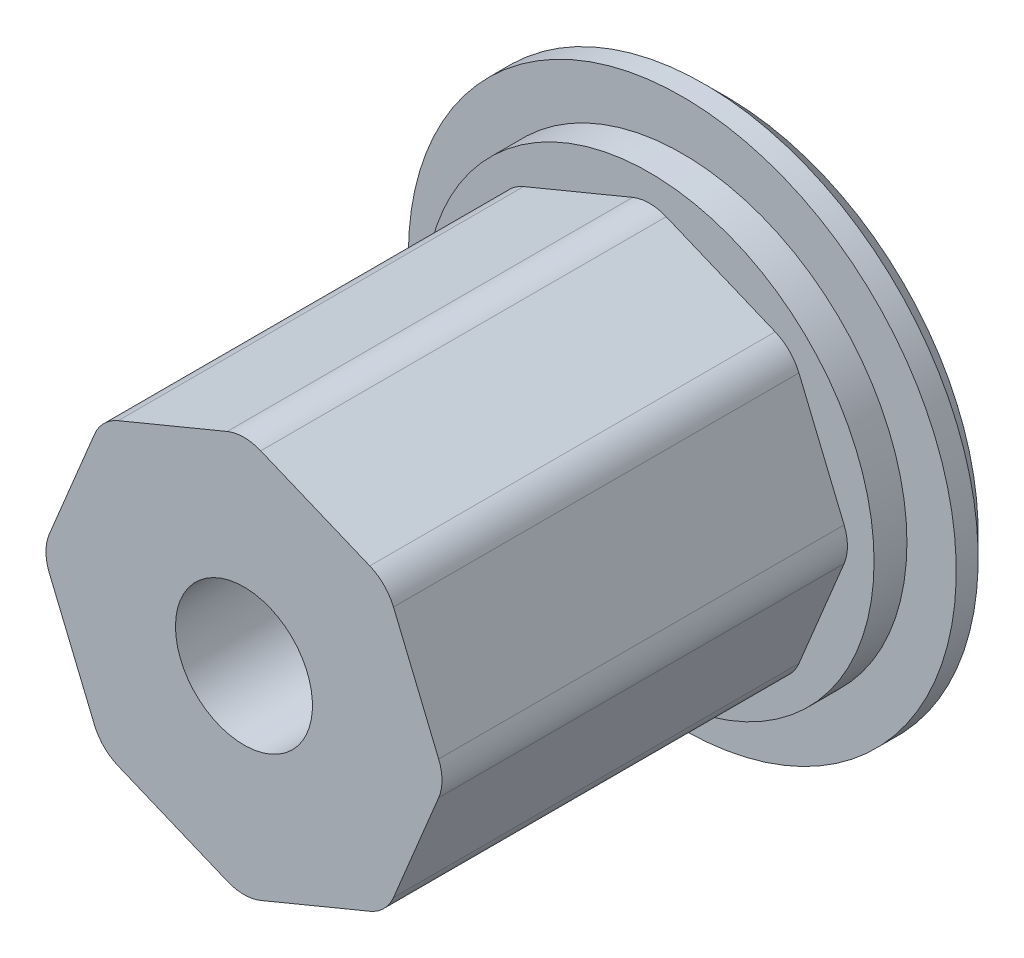
SolidWorks part; units mm, degrees
material "1.2210 (115CrV3)"
ref_plane "Front Plane" through (0, 0, 0) normal (0, 0, 1) x (1, 0, 0)
ref_plane "Top Plane" through (0, 0, 0) normal (0, 1, 0) x (1, 0, 0)
ref_plane "Right Plane" through (0, 0, 0) normal (1, 0, 0) x (0, 0, -1)
sketch "Sketch1" plane through (0, 0, 0) normal (0, 0, 1) x (1, 0, 0)
  line L0 (-12.5, 10.5) -> (-12.5, -10.5)
  line L1 (-10.5, 12.5) -> (10.5, 12.5)
  line L2 (-10.5, -12.5) -> (10.5, -12.5)
  line L3 (12.5, 10.5) -> (12.5, -10.5)
  line L4 (-12.5, 12.5) -> (12.5, -12.5) construction
  line L5 (-12.5, -12.5) -> (12.5, 12.5) construction
  line L6 (0, -14.0711) -> (0, 14.0711) construction
  line L7 (-13.6453, 11.4805) -> (-17.7666, 1.5307)
  line L8 (-17.7666, -1.5307) -> (-13.6453, -11.4805)
  line L9 (-11.4805, -13.6453) -> (-1.5307, -17.7666)
  line L10 (1.5307, -17.7666) -> (11.4805, -13.6453)
  line L11 (13.6453, -11.4805) -> (17.7666, -1.5307)
  line L12 (17.7666, 1.5307) -> (13.6453, 11.4805)
  line L13 (11.4805, 13.6453) -> (1.5307, 17.7666)
  line L14 (-1.5307, 17.7666) -> (-11.4805, 13.6453)
  circle A0 centre (0, 0) radius 17 construction
  arc A1 (10.5, -12.5) -> (12.5, -10.5) centre (10.5, -10.5) ccw
  arc A2 (-12.5, -10.5) -> (-10.5, -12.5) centre (-10.5, -10.5) ccw
  arc A3 (10.5, 12.5) -> (12.5, 10.5) centre (10.5, 10.5) cw
  arc A4 (-10.5, 12.5) -> (-12.5, 10.5) centre (-10.5, 10.5) ccw
  arc A5 (-13.6453, 11.4805) -> (-11.4805, 13.6453) centre (-9.9498, 9.9498) cw
  arc A6 (-17.7666, 1.5307) -> (-17.7666, -1.5307) centre (-14.0711, 0) ccw
  arc A7 (-13.6453, -11.4805) -> (-11.4805, -13.6453) centre (-9.9498, -9.9498) ccw
  arc A8 (-1.5307, -17.7666) -> (1.5307, -17.7666) centre (0, -14.0711) ccw
  arc A9 (11.4805, -13.6453) -> (13.6453, -11.4805) centre (9.9498, -9.9498) ccw
  arc A10 (17.7666, -1.5307) -> (17.7666, 1.5307) centre (14.0711, 0) ccw
  arc A11 (13.6453, 11.4805) -> (11.4805, 13.6453) centre (9.9498, 9.9498) ccw
  arc A12 (1.5307, 17.7666) -> (-1.5307, 17.7666) centre (0, 14.0711) ccw
  point P43 (0, 0)
  dimension "D1" = 2
  dimension "D3" = 4
  dimension "D4" = 34
  dimension "D2" = 25
extrude "Boss-Extrude1" add sketch "Sketch1" along normal blind 23
sketch "Sketch3" plane through (0, 0, 23) normal (0, 0, 1) x (1, 0, 0)
  line L8 (-1.5307, 17.7666) -> (-11.4805, 13.6453)
  line L9 (11.4805, 13.6453) -> (1.5307, 17.7666)
  line L10 (17.7666, 1.5307) -> (13.6453, 11.4805)
  line L11 (13.6453, -11.4805) -> (17.7666, -1.5307)
  line L12 (1.5307, -17.7666) -> (11.4805, -13.6453)
  line L13 (-11.4805, -13.6453) -> (-1.5307, -17.7666)
  line L14 (-17.7666, -1.5307) -> (-13.6453, -11.4805)
  line L15 (-13.6453, 11.4805) -> (-17.7666, 1.5307)
  line L16 (-1.5307, 17.7666) -> (-11.4805, 13.6453)
  line L17 (11.4805, 13.6453) -> (1.5307, 17.7666)
  line L18 (17.7666, 1.5307) -> (13.6453, 11.4805)
  line L19 (13.6453, -11.4805) -> (17.7666, -1.5307)
  line L20 (1.5307, -17.7666) -> (11.4805, -13.6453)
  line L21 (-11.4805, -13.6453) -> (-1.5307, -17.7666)
  line L22 (-17.7666, -1.5307) -> (-13.6453, -11.4805)
  line L23 (-13.6453, 11.4805) -> (-17.7666, 1.5307)
  circle A0 centre (0, 0) radius 6.25
  arc A8 (-11.4805, 13.6453) -> (-13.6453, 11.4805) centre (-9.9498, 9.9498) ccw
  arc A9 (1.5307, 17.7666) -> (-1.5307, 17.7666) centre (0, 14.0711) ccw
  arc A10 (13.6453, 11.4805) -> (11.4805, 13.6453) centre (9.9498, 9.9498) ccw
  arc A11 (17.7666, -1.5307) -> (17.7666, 1.5307) centre (14.0711, 0) ccw
  arc A12 (11.4805, -13.6453) -> (13.6453, -11.4805) centre (9.9498, -9.9498) ccw
  arc A13 (-1.5307, -17.7666) -> (1.5307, -17.7666) centre (0, -14.0711) ccw
  arc A14 (-13.6453, -11.4805) -> (-11.4805, -13.6453) centre (-9.9498, -9.9498) ccw
  arc A15 (-17.7666, 1.5307) -> (-17.7666, -1.5307) centre (-14.0711, 0) ccw
  arc A16 (-11.4805, 13.6453) -> (-13.6453, 11.4805) centre (-9.9498, 9.9498) ccw
  arc A17 (1.5307, 17.7666) -> (-1.5307, 17.7666) centre (0, 14.0711) ccw
  arc A18 (13.6453, 11.4805) -> (11.4805, 13.6453) centre (9.9498, 9.9498) ccw
  arc A19 (17.7666, -1.5307) -> (17.7666, 1.5307) centre (14.0711, 0) ccw
  arc A20 (11.4805, -13.6453) -> (13.6453, -11.4805) centre (9.9498, -9.9498) ccw
  arc A21 (-1.5307, -17.7666) -> (1.5307, -17.7666) centre (0, -14.0711) ccw
  arc A22 (-13.6453, -11.4805) -> (-11.4805, -13.6453) centre (-9.9498, -9.9498) ccw
  arc A23 (-17.7666, 1.5307) -> (-17.7666, -1.5307) centre (-14.0711, 0) ccw
  dimension "D2" = 12.5
  dimension "D1" = 0
extrude "Boss-Extrude2" add sketch "Sketch3" along normal offset from surface (17 mm away) 40 up to face at (0, 0, 0)
sketch "Sketch7" plane through (0, 0, 0) normal (0, 0, -1) x (-1, 0, 0)
  line L1 (-11.4805, 13.6453) -> (-1.5307, 17.7666) construction
  line L2 (-17.7666, 1.5307) -> (-13.6453, 11.4805) construction
  line L3 (-13.6453, -11.4805) -> (-17.7666, -1.5307) construction
  line L4 (-1.5307, -17.7666) -> (-11.4805, -13.6453) construction
  line L5 (11.4805, -13.6453) -> (1.5307, -17.7666) construction
  line L6 (17.7666, -1.5307) -> (13.6453, -11.4805) construction
  line L7 (13.6453, 11.4805) -> (17.7666, 1.5307) construction
  line L8 (1.5307, 17.7666) -> (11.4805, 13.6453) construction
  line L9 (-11.4805, 13.6453) -> (-1.5307, 17.7666)
  line L10 (-17.7666, 1.5307) -> (-13.6453, 11.4805)
  line L11 (-13.6453, -11.4805) -> (-17.7666, -1.5307)
  line L12 (-1.5307, -17.7666) -> (-11.4805, -13.6453)
  line L13 (11.4805, -13.6453) -> (1.5307, -17.7666)
  line L14 (17.7666, -1.5307) -> (13.6453, -11.4805)
  line L15 (13.6453, 11.4805) -> (17.7666, 1.5307)
  line L16 (1.5307, 17.7666) -> (11.4805, 13.6453)
  circle A0 centre (0, 0) radius 20.5
  arc A1 (-11.4805, 13.6453) -> (-13.6453, 11.4805) centre (-9.9498, 9.9498) ccw construction
  arc A2 (-17.7666, 1.5307) -> (-17.7666, -1.5307) centre (-14.0711, 0) ccw construction
  arc A3 (-13.6453, -11.4805) -> (-11.4805, -13.6453) centre (-9.9498, -9.9498) ccw construction
  arc A4 (-1.5307, -17.7666) -> (1.5307, -17.7666) centre (0, -14.0711) ccw construction
  arc A5 (11.4805, -13.6453) -> (13.6453, -11.4805) centre (9.9498, -9.9498) ccw construction
  arc A6 (17.7666, -1.5307) -> (17.7666, 1.5307) centre (14.0711, 0) ccw construction
  arc A7 (13.6453, 11.4805) -> (11.4805, 13.6453) centre (9.9498, 9.9498) ccw construction
  arc A8 (1.5307, 17.7666) -> (-1.5307, 17.7666) centre (0, 14.0711) ccw construction
  arc A9 (-11.4805, 13.6453) -> (-13.6453, 11.4805) centre (-9.9498, 9.9498) ccw
  arc A10 (-17.7666, 1.5307) -> (-17.7666, -1.5307) centre (-14.0711, 0) ccw
  arc A11 (-13.6453, -11.4805) -> (-11.4805, -13.6453) centre (-9.9498, -9.9498) ccw
  arc A12 (-1.5307, -17.7666) -> (1.5307, -17.7666) centre (0, -14.0711) ccw
  arc A13 (11.4805, -13.6453) -> (13.6453, -11.4805) centre (9.9498, -9.9498) ccw
  arc A14 (17.7666, -1.5307) -> (17.7666, 1.5307) centre (14.0711, 0) ccw
  arc A15 (13.6453, 11.4805) -> (11.4805, 13.6453) centre (9.9498, 9.9498) ccw
  arc A16 (1.5307, 17.7666) -> (-1.5307, 17.7666) centre (0, 14.0711) ccw
  dimension "D1" = 41
extrude "Boss-Extrude3" add sketch "Sketch7" against normal blind 3
sketch "Sketch10" plane through (0, 0, 0) normal (0, 0, -1) x (-1, 0, 0)
  circle A0 centre (0, 0) radius 18
  circle A1 centre (0, 0) radius 25
  dimension "D1" = 50
  dimension "D2" = 36
extrude "Boss-Extrude4" add sketch "Sketch10" along normal blind 4
chamfer "Chamfer1" distance 4 angle 45 1 edges at (-18, 0, 0)
sketch "Sketch11" plane through (0, 0, 0) normal (0, 1, 0) x (0, 0, -1)
  line L0 (0, 14) -> (-3.0876, 10.9124)
  line L1 (-3.0876, 10.9124) -> (0, 10.9124)
  line L2 (0, 10.9124) -> (0, 14)
  line L6 (0, 0) -> (5.9352, 0) construction
revolve "Cut-Revolve1" cut sketch "Sketch11" angle 360 about L6
chamfer "Chamfer2" distance 2 angle 45 1 edges at (-25, 0, -4)
chamfer "Chamfer3" distance 3 angle 45 1 edges at (6.25, 0, 23)
sketch "Sketch12" plane through (0, 0, 23) normal (0, 0, -1) x (-1, 0, 0)
  line L0 (-10.1469, 12.5) -> (-10.5, 12.5)
  line L1 (-12.5, -10.1469) -> (-12.5, -10.5)
  line L2 (10.1469, -12.5) -> (10.5, -12.5)
  line L3 (12.5, 10.1469) -> (12.5, 10.5)
  line L4 (-10.5, -12.5) -> (10.5, -12.5)
  line L5 (12.5, -10.5) -> (12.5, 10.5)
  line L6 (10.5, 12.5) -> (-10.5, 12.5)
  line L7 (-12.5, 10.5) -> (-12.5, -10.5)
  line L8 (-10.5, -12.5) -> (-10.1469, -12.5)
  line L9 (12.5, -10.5) -> (12.5, -10.1469)
  line L10 (10.5, 12.5) -> (10.1469, 12.5)
  line L11 (-12.5, 10.5) -> (-12.5, 10.1469)
  arc A0 (-12.5, -10.1469) -> (-10.1469, -12.5) centre (0, 0) ccw
  arc A1 (10.1469, -12.5) -> (12.5, -10.1469) centre (0, 0) ccw
  arc A3 (12.5, 10.1469) -> (10.1469, 12.5) centre (0, 0) ccw
  arc A4 (-10.1469, 12.5) -> (-12.5, 10.1469) centre (0, 0) ccw
  arc A6 (-12.5, -10.5) -> (-10.5, -12.5) centre (-10.5, -10.5) ccw
  arc A7 (10.5, -12.5) -> (12.5, -10.5) centre (10.5, -10.5) ccw
  arc A8 (12.5, 10.5) -> (10.5, 12.5) centre (10.5, 10.5) ccw
  arc A9 (-10.5, 12.5) -> (-12.5, 10.5) centre (-10.5, 10.5) ccw
  arc A10 (-12.5, -10.5) -> (-10.5, -12.5) centre (-10.5, -10.5) ccw
  arc A11 (10.5, -12.5) -> (12.5, -10.5) centre (10.5, -10.5) ccw
  arc A12 (12.5, 10.5) -> (10.5, 12.5) centre (10.5, 10.5) ccw
  arc A13 (-10.5, 12.5) -> (-12.5, 10.5) centre (-10.5, 10.5) ccw
  dimension "D2" = 32.2
  dimension "D1" = 0
extrude "Boss-Extrude5" add sketch "Sketch12" along normal up to surface (25.1 mm away)
fillet "Fillet2" radius 3 8 edges at (-12.5, 10.1469, 10.45) (-10.1469, 12.5, 10.45) (-10.1469, -12.5, 10.45) (-12.5, -10.1469, 10.45) (10.1469, -12.5, 10.45) (12.5, -10.1469, 10.45) (12.5, 10.1469, 10.45) (10.1469, 12.5, 10.45)
